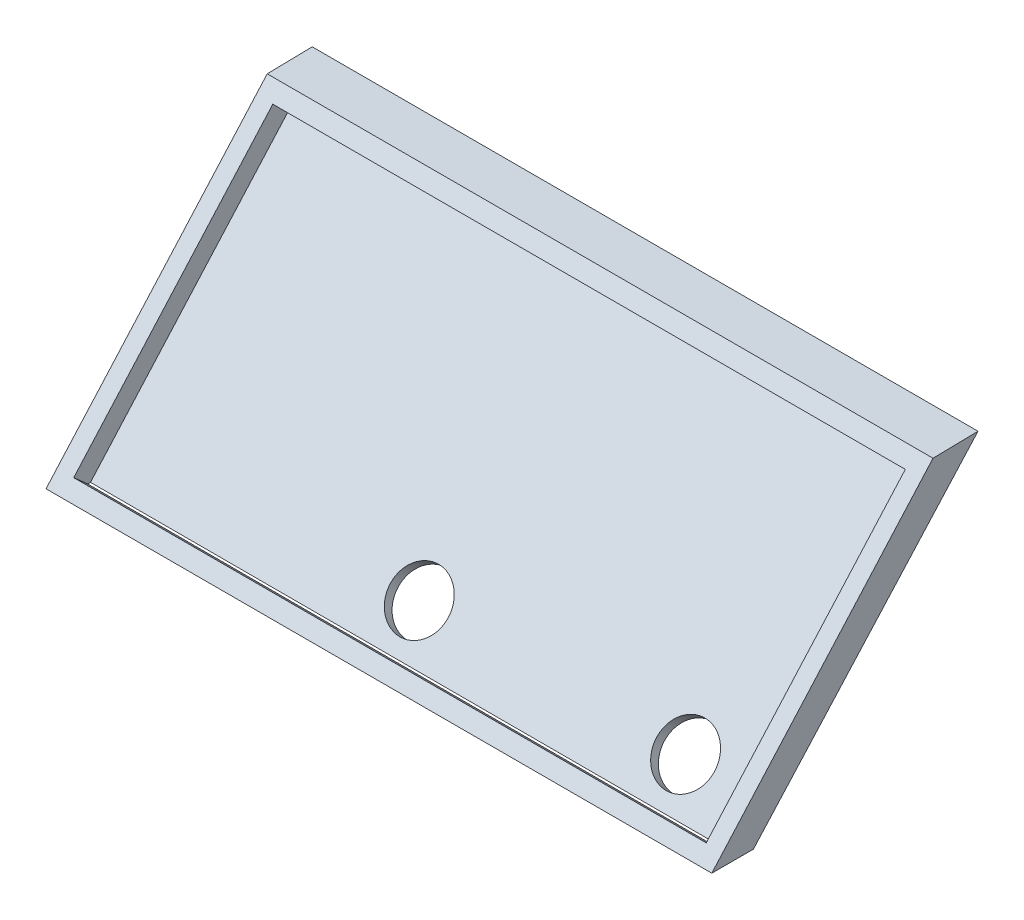
SolidWorks part; units mm, degrees
ref_plane "Front Plane" through (0, 0, 0) normal (0, 0, 1) x (1, 0, 0)
ref_plane "Top Plane" through (0, 0, 0) normal (0, 1, 0) x (1, 0, 0)
ref_plane "Right Plane" through (0, 0, 0) normal (1, 0, 0) x (0, 0, -1)
sketch "Sketch1" plane through (0, 0, 0) normal (0, 0, 1) x (1, 0, 0)
  line L1 (50.8, -25.4) -> (-50.8, -25.4)
  line L2 (50.8, -25.4) -> (50.8, 25.4)
  line L3 (50.8, 25.4) -> (-50.8, 25.4)
  line L4 (-50.8, -25.4) -> (-50.8, 25.4)
  line L5 (50.8, -25.4) -> (-50.8, 25.4) construction
  line L6 (50.8, 25.4) -> (-50.8, -25.4) construction
  point P0 (0, 0)
  dimension "D1" = 101.6
  dimension "D2" = 50.8
extrude "Boss-Extrude1" add sketch "Sketch1" against normal blind 228.6
sketch "Sketch2" plane through (0, 25.4, 0) normal (0, 1, 0) x (1, 0, 0)
  line L0 (0, 0) -> (0, 228.6) construction
  line L1 (50.8, 228.6) -> (-50.8, 228.6) construction
  line L3 (48.26, 200.66) -> (-48.26, 200.66)
  line L4 (48.26, 200.66) -> (48.26, 27.94)
  line L5 (48.26, 27.94) -> (-48.26, 27.94)
  line L6 (-48.26, 200.66) -> (-48.26, 27.94)
  line L7 (48.26, 200.66) -> (-48.26, 27.94) construction
  line L8 (48.26, 27.94) -> (-48.26, 200.66) construction
  point P6 (0, 114.3)
  dimension "D1" = 172.72
  dimension "D2" = 96.52
extrude "Cut-Extrude1" cut sketch "Sketch2" against normal blind 50.8
sketch "Sketch3" plane through (0, 25.4, 0) normal (0, 1, 0) x (1, 0, 0)
  line L0 (0, 0) -> (0, 76.1763)
  line L1 (-48.26, 200.66) -> (-48.26, 27.94) construction
  line L2 (48.26, 79.3513) -> (-48.26, 79.3513)
  line L3 (48.26, 79.3513) -> (48.26, 73.0013)
  line L4 (48.26, 73.0013) -> (-48.26, 73.0013)
  line L5 (-48.26, 79.3513) -> (-48.26, 73.0013)
  line L6 (48.26, 79.3513) -> (-48.26, 73.0013) construction
  line L7 (48.26, 73.0013) -> (-48.26, 79.3513) construction
  line M2 (-48.26, 27.94) -> (-48.26, 200.66)
  line M4 (48.26, 200.66) -> (48.26, 27.94)
  dimension "D1" = 6.35
extrude "Boss-Extrude2" add sketch "Sketch3" against normal blind 50.8 contours L4 L2 M4 M2 region at (47.2927, 25.4, -76.1763)
sketch "Sketch5" plane through (0, 25.4, 0) normal (0, 1, 0) x (1, 0, 0)
  line L0 (48.26, 73.0013) -> (50.8, 73.0013) construction
  line L3 (50.8, 228.6) -> (50.8, 0) construction
sketch "Sketch6" plane through (50.8, 0, 0) normal (1, 0, 0) x (0, 0, -1)
  line L0 (73.0013, 25.4) -> (106.7566, 63.3634)
  dimension "D1" = 50.8
sketch "Sketch7" plane through (0, 25.4, 0) normal (0, 1, 0) x (1, 0, 0)
  line L0 (48.26, 79.3513) -> (50.8, 79.3513)
  line L1 (50.8, 73.0013) -> (50.8, 106.7566) construction
sketch "Sketch8" plane through (50.8, 0, 0) normal (1, 0, 0) x (0, 0, -1)
  line L0 (79.3513, 25.4) -> (113.6226, 63.5)
  line L2 (106.7566, 63.3634) -> (113.6226, 63.5)
  dimension "D1" = 38.1
sketch "Sketch9" plane through (50.8, 0, 0) normal (1, 0, 0) x (0, 0, -1)
  line L0 (73.0013, 25.4) -> (79.3513, 25.4)
sketch "Sketch10" plane through (0, 25.4, 0) normal (0, 1, 0) x (1, 0, 0)
  line L0 (-48.26, 79.3513) -> (-50.8, 79.3513)
  line L1 (-50.8, 228.6) -> (-50.8, 0) construction
  line L2 (-48.26, 73.0013) -> (-50.8, 73.0013)
sketch "Sketch11" plane through (-50.8, 0, 0) normal (-1, 0, 0) x (0, 0, 1)
  line L0 (-79.3513, 25.4) -> (-113.6226, 63.5)
  line L1 (-73.0013, 25.4) -> (-106.7566, 63.3634)
  line L2 (-106.7566, 63.3634) -> (-113.6226, 63.5)
  line L3 (-79.3513, 25.4) -> (-73.0013, 25.4)
extrude "Boss-Extrude3" add sketch "Sketch11" against normal up to vertex (101.6 mm away) contours L1 L2 L0 L3 up to point (50.8, 63.3634, -106.7566)
sketch "Sketch13" plane through (0, 25.4, 0) normal (0, 1, 0) x (1, 0, 0)
  line L1 (-48.26, 200.66) -> (48.26, 200.66)
  line L2 (-48.26, 200.66) -> (-48.26, 226.06)
  line L3 (-48.26, 226.06) -> (48.26, 226.06)
  line L4 (48.26, 200.66) -> (48.26, 226.06)
  dimension "D1" = 25.4
extrude "Cut-Extrude2" cut sketch "Sketch13" against normal blind 50.8
sketch "Sketch14" plane through (0, 25.4, 0) normal (0, 1, 0) x (1, 0, 0)
  line L1 (-48.26, 27.94) -> (48.26, 27.94)
  line L2 (-48.26, 27.94) -> (-48.26, 2.54)
  line L3 (-48.26, 2.54) -> (48.26, 2.54)
  line L4 (48.26, 27.94) -> (48.26, 2.54)
  dimension "D1" = 96.52
  dimension "D2" = 25.4
extrude "Cut-Extrude3" cut sketch "Sketch14" against normal blind 50.8
sketch "Sketch15" plane through (0, 0, -73.0013) normal (0, 0, 1) x (1, 0, 0)
  line L1 (48.26, -25.4) -> (-48.26, -25.4)
  line L2 (48.26, -25.4) -> (48.26, 25.4)
  line L3 (48.26, 25.4) -> (-48.26, 25.4)
  line L4 (-48.26, -25.4) -> (-48.26, 25.4)
  line L5 (48.26, -25.4) -> (-48.26, 25.4) construction
  line L6 (48.26, 25.4) -> (-48.26, -25.4) construction
  point P0 (0, 0)
  dimension "D1" = 96.52
  dimension "D2" = 50.8
extrude "Cut-Extrude6" cut sketch "Sketch15" against normal blind 6.35
sketch "Sketch16" plane through (0, -25.0354, -28.1564) normal (0, 0.6645, 0.7473) x (1, 0, 0)
  line L0 (0, 67.4892) -> (0, 118.2892) construction
  line L1 (48.26, 67.4892) -> (-48.26, 67.4892) construction
  line L2 (50.8, 118.2892) -> (-50.8, 118.2892) construction
  line L4 (48.26, 70.0292) -> (-48.26, 70.0292)
  line L5 (48.26, 70.0292) -> (48.26, 115.7492)
  line L6 (48.26, 115.7492) -> (-48.26, 115.7492)
  line L7 (-48.26, 70.0292) -> (-48.26, 115.7492)
  line L8 (48.26, 70.0292) -> (-48.26, 115.7492) construction
  line L9 (48.26, 115.7492) -> (-48.26, 70.0292) construction
  point P7 (0, 92.8892)
  dimension "D1" = 96.52
  dimension "D2" = 45.72
extrude "Cut-Extrude7" cut sketch "Sketch16" against normal blind 3.175
sketch "Sketch17" plane through (0, 0, 0) normal (0, 0, 1) x (1, 0, 0)
  line L0 (50.8, 0) -> (-50.8, 0)
  line L1 (-50.8, 25.4) -> (-50.8, -25.4) construction
  line L4 (-50.8, 0) -> (-50.8, -25.4)
  line L5 (-50.8, -25.4) -> (50.8, -25.4)
  line L6 (50.8, 0) -> (50.8, -25.4)
  point P6 (0, 0)
extrude "Cut-Extrude8" cut sketch "Sketch17" against normal blind 228.6
sketch "Sketch18" plane through (48.26, 0, 0) normal (-1, 0, 0) x (0, 0, 1)
  line L0 (-73.0013, 25.4) -> (-73.0013, 0) construction
  line L1 (-228.6, 0) -> (0, 0) construction
  line L2 (-79.3513, 25.4) -> (-79.3513, 0) construction
  line L3 (-79.3513, 0) -> (-73.0013, 0) construction
  line L4 (-73.0013, 12.7) -> (-79.3513, 12.7) construction
sketch "Sketch19" plane through (48.26, 0, 0) normal (-1, 0, 0) x (0, 0, 1)
  line L0 (-73.0013, 12.7) -> (-79.3513, 12.7)
  line L1 (-79.3513, 12.7) -> (-79.3513, 0)
  line L2 (-79.3513, 0) -> (-73.0013, 0)
  line L3 (-73.0013, 12.7) -> (-73.0013, 0)
extrude "Boss-Extrude4" add sketch "Sketch19" along normal blind 96.52
sketch "Sketch20" plane through (-50.8, 0, 0) normal (-1, 0, 0) x (0, 0, 1)
  line L0 (-228.6, 0) -> (-177.8, 0)
  line L1 (-228.6, 0) -> (0, 0) construction
  line L3 (-177.8, 0) -> (-171.45, 0)
  line L4 (-177.8, 0) -> (-177.8, 12.7)
  line L5 (-177.8, 12.7) -> (-171.45, 12.7)
  line L6 (-171.45, 0) -> (-171.45, 12.7)
  line M4 (-228.6, 0) -> (0, 0)
  dimension "D1" = 50.8
  dimension "D2" = 6.35
  dimension "D3" = 12.7
extrude "Boss-Extrude5" add sketch "Sketch20" against normal blind 101.6 contours L6 L5 L4 M4 region at (-50.8, 6.35, -174.625)
sketch "Sketch24" plane through (0, 0, 0) normal (0, -1, 0) x (1, 0, 0)
  line L0 (48.26, -79.3513) -> (-48.26, -79.3513) construction
  line L1 (50.8, -73.0013) -> (38.1, -73.0013)
  line L2 (50.8, -73.0013) -> (50.8, -79.3513)
  line L3 (50.8, -79.3513) -> (38.1, -79.3513)
  line L4 (38.1, -73.0013) -> (38.1, -79.3513)
  dimension "D1" = 12.7
extrude "Boss-Extrude8" add sketch "Sketch24" along normal blind 19.05
sketch "Sketch25" plane through (0, 0, 0) normal (0, -1, 0) x (1, 0, 0)
  line L0 (-48.26, -79.3513) -> (38.1, -79.3513) construction
  line L1 (-50.8, -73.0013) -> (-38.1, -73.0013)
  line L2 (-50.8, -73.0013) -> (-50.8, -79.3513)
  line L3 (-50.8, -79.3513) -> (-38.1, -79.3513)
  line L4 (-38.1, -73.0013) -> (-38.1, -79.3513)
  dimension "D1" = 12.7
extrude "Boss-Extrude9" add sketch "Sketch25" along normal blind 19.05
sketch "Sketch26" plane through (0, 0, 0) normal (0, -1, 0) x (1, 0, 0)
  line L0 (-50.8, -228.6) -> (-50.8, -79.3513) construction
  line L1 (-50.8, -171.45) -> (-38.1, -171.45)
  line L2 (-50.8, -171.45) -> (-50.8, -177.8)
  line L3 (-50.8, -177.8) -> (-38.1, -177.8)
  line L4 (-38.1, -171.45) -> (-38.1, -177.8)
  line L5 (48.26, -177.8) -> (-48.26, -177.8) construction
  dimension "D1" = 12.7
extrude "Boss-Extrude10" add sketch "Sketch26" along normal blind 19.05
sketch "Sketch27" plane through (0, 0, 0) normal (0, -1, 0) x (1, 0, 0)
  line L0 (50.8, -228.6) -> (50.8, -79.3513) construction
  line L1 (50.8, -177.8) -> (38.1, -177.8)
  line L2 (50.8, -177.8) -> (50.8, -171.45)
  line L3 (50.8, -171.45) -> (38.1, -171.45)
  line L4 (38.1, -177.8) -> (38.1, -171.45)
  line L5 (48.26, -171.45) -> (-38.1, -171.45) construction
  dimension "D1" = 12.7
extrude "Boss-Extrude11" add sketch "Sketch27" along normal blind 19.05
sketch "Sketch28" plane through (0, 0, -73.0013) normal (0, 0, 1) x (1, 0, 0)
  line L0 (50.8, 0) -> (-50.8, 0) construction
  line L1 (50.8, -19.05) -> (41.91, -19.05)
  line L2 (50.8, -19.05) -> (50.8, 0)
  line L3 (50.8, 0) -> (41.91, 0)
  line L4 (41.91, -19.05) -> (41.91, 0)
  dimension "D1" = 8.89
extrude "Cut-Extrude9" cut sketch "Sketch28" against normal blind 6.35
sketch "Sketch29" plane through (0, 0, -73.0013) normal (0, 0, 1) x (1, 0, 0)
  line L0 (50.8, 0) -> (-50.8, 0) construction
  line L1 (-50.8, -19.05) -> (-41.91, -19.05)
  line L2 (-50.8, -19.05) -> (-50.8, 0)
  line L3 (-50.8, 0) -> (-41.91, 0)
  line L4 (-41.91, -19.05) -> (-41.91, 0)
  dimension "D1" = 8.89
extrude "Cut-Extrude10" cut sketch "Sketch29" against normal blind 6.35
sketch "Sketch30" plane through (0, 0, -171.45) normal (0, 0, 1) x (1, 0, 0)
  line L1 (-50.8, -19.05) -> (-41.91, -19.05)
  line L2 (-50.8, -19.05) -> (-50.8, 0)
  line L3 (-50.8, 0) -> (-41.91, 0)
  line L4 (-41.91, -19.05) -> (-41.91, 0)
extrude "Cut-Extrude11" cut sketch "Sketch30" against normal blind 6.35
sketch "Sketch31" plane through (0, 0, -171.45) normal (0, 0, 1) x (1, 0, 0)
  line L0 (41.91, 0) -> (41.91, -19.05) construction
  line L1 (50.8, -19.05) -> (41.91, -19.05)
  line L2 (50.8, -19.05) -> (50.8, 0)
  line L3 (50.8, 0) -> (41.91, 0)
  line L4 (41.91, -19.05) -> (41.91, 0)
extrude "Cut-Extrude12" cut sketch "Sketch31" against normal blind 6.35
sketch "Sketch33" plane through (0, 0, -2.54) normal (0, 0, -1) x (-1, 0, 0)
  line L1 (48.26, 0) -> (48.26, 25.4) construction
  line L2 (48.26, 12.7) -> (-48.26, 12.7) construction
  line L3 (-48.26, 0) -> (-48.26, 25.4) construction
  line L5 (48.26, 13.97) -> (-48.26, 13.97)
  line L6 (48.26, 13.97) -> (48.26, 11.43)
  line L7 (48.26, 11.43) -> (-48.26, 11.43)
  line L8 (-48.26, 13.97) -> (-48.26, 11.43)
  line L9 (48.26, 13.97) -> (-48.26, 11.43) construction
  line L10 (48.26, 11.43) -> (-48.26, 13.97) construction
  point P6 (0, 12.7)
  dimension "D1" = 2.54
extrude "Boss-Extrude13" add sketch "Sketch33" along normal blind 2.54
sketch "Sketch34" plane through (0, 0, -226.06) normal (0, 0, 1) x (1, 0, 0)
  line L0 (0, 0) -> (0, 25.4) construction
  line L1 (-48.26, 0) -> (-48.26, 25.4) construction
  line L2 (48.26, 12.7) -> (-48.26, 12.7) construction
  line L3 (48.26, 0) -> (48.26, 25.4) construction
  line L4 (-48.26, 0) -> (48.26, 0) construction
  line L5 (48.26, 25.4) -> (-48.26, 25.4) construction
  line L7 (48.26, 13.97) -> (-48.26, 13.97)
  line L8 (48.26, 13.97) -> (48.26, 11.43)
  line L9 (48.26, 11.43) -> (-48.26, 11.43)
  line L10 (-48.26, 13.97) -> (-48.26, 11.43)
  line L11 (48.26, 13.97) -> (-48.26, 11.43) construction
  line L12 (48.26, 11.43) -> (-48.26, 13.97) construction
  point P12 (0, 12.7)
  dimension "D1" = 2.54
extrude "Boss-Extrude17" add sketch "Sketch34" along normal blind 2.54
sketch "Sketch36" plane through (-48.26, 0, 0) normal (1, 0, 0) x (0, 0, -1)
  line L0 (5.08, 11.43) -> (5.08, 13.97) construction
  line L1 (5.08, 13.97) -> (223.52, 13.97)
  line L2 (5.08, 13.97) -> (5.08, 11.43)
  line L3 (5.08, 11.43) -> (223.52, 11.43)
  line L4 (223.52, 13.97) -> (223.52, 11.43)
extrude "Boss-Extrude18" add sketch "Sketch36" along normal blind 2.54
sketch "Sketch37" plane through (48.26, 0, 0) normal (-1, 0, 0) x (0, 0, 1)
  line L1 (-5.08, 13.97) -> (-223.52, 13.97)
  line L2 (-5.08, 13.97) -> (-5.08, 11.43)
  line L3 (-5.08, 11.43) -> (-223.52, 11.43)
  line L4 (-223.52, 13.97) -> (-223.52, 11.43)
extrude "Boss-Extrude19" add sketch "Sketch37" along normal blind 2.54
sketch "Sketch42" plane through (-41.91, 0, 0) normal (-1, 0, 0) x (0, 0, 1)
  line L0 (-73.0013, -19.05) -> (-73.0013, 0) construction
  line L1 (-73.0013, -12.7) -> (-79.3513, -12.7)
  line L2 (-73.0013, -12.7) -> (-73.0013, -19.05)
  line L3 (-73.0013, -19.05) -> (-79.3513, -19.05)
  line L4 (-79.3513, -12.7) -> (-79.3513, -19.05)
  line L5 (-79.3513, -19.05) -> (-79.3513, 0) construction
extrude "Cut-Extrude16" cut sketch "Sketch42" against normal blind 5.08
sketch "Sketch45" plane through (0, 0, 0) normal (0, 0, 1) x (1, 0, 0)
  line L0 (-50.8, 12.7) -> (50.8, 12.7) construction
  line L1 (-50.8, 25.4) -> (-50.8, 0) construction
  line L2 (50.8, 0) -> (50.8, 25.4) construction
  line L3 (0, 0) -> (0, 25.4) construction
  line L4 (48.26, 25.4) -> (-48.26, 25.4) construction
  line L5 (0, 12.7) -> (-50.8, 12.7) construction
  line L6 (-25.0661, 12.7) -> (-50.8, 12.7) construction
  line L7 (44.537, 17.78) -> (44.537, 7.62)
  line L8 (-31.329, 17.78) -> (-44.537, 17.78)
  line L9 (-31.329, 17.78) -> (-31.329, 7.62)
  line L10 (-31.329, 7.62) -> (-44.537, 7.62)
  line L11 (-44.537, 17.78) -> (-44.537, 7.62)
  line L12 (-31.329, 17.78) -> (-44.537, 7.62) construction
  line L13 (-31.329, 7.62) -> (-44.537, 17.78) construction
  line L14 (31.329, 7.62) -> (44.537, 7.62)
  line L15 (31.329, 17.78) -> (31.329, 7.62)
  line L16 (31.329, 17.78) -> (44.537, 17.78)
  point P13 (-37.933, 12.7)
  dimension "D1" = 13.208
  dimension "D2" = 10.16
extrude "Cut-Extrude19" cut sketch "Sketch45" against normal blind 6.35
sketch "Sketch50" plane through (-41.91, 0, 0) normal (-1, 0, 0) x (0, 0, 1)
  line L0 (-79.3513, -12.7) -> (-79.3513, -19.05)
  line L1 (-73.0013, -12.7) -> (-73.0013, -19.05)
  line L2 (-79.3513, -19.05) -> (-73.0013, -19.05)
  line L7 (-79.3513, 0) -> (-79.3513, -12.7)
  line L8 (-79.3513, -12.7) -> (-73.0013, -12.7)
  line L9 (-73.0013, -12.7) -> (-73.0013, 0)
  line L10 (-73.0013, 0) -> (-79.3513, 0)
  line L12 (-79.3513, -12.7) -> (-73.0013, -12.7)
  dimension "D1" = 6.35
  dimension "D2" = 0
extrude "Boss-Extrude20" add sketch "Sketch50" against normal blind 3.81 contours L0 L2 L1 L12
sketch "Sketch51" plane through (-41.91, 0, 0) normal (-1, 0, 0) x (0, 0, 1)
  line L0 (-79.3513, -19.05) -> (-79.3513, -25.4)
  line L1 (-73.0013, -19.05) -> (-73.0013, -25.4)
  line L2 (-73.0013, -25.4) -> (-79.3513, -25.4)
  line L7 (-79.3513, 0) -> (-79.3513, -19.05)
  line L8 (-79.3513, -19.05) -> (-73.0013, -19.05)
  line L9 (-73.0013, -19.05) -> (-73.0013, 0)
  line L10 (-73.0013, 0) -> (-79.3513, 0)
  line L12 (-79.3513, -19.05) -> (-73.0013, -19.05)
  dimension "D1" = 6.35
  dimension "D2" = 0
extrude "Boss-Extrude21" add sketch "Sketch51" against normal blind 3.81
sketch "Sketch52" plane through (-41.91, 0, 0) normal (-1, 0, 0) x (0, 0, 1)
  line L0 (-177.8, -19.05) -> (-177.8, -25.4)
  line L1 (-171.45, -19.05) -> (-171.45, -25.4)
  line L2 (-171.45, -25.4) -> (-177.8, -25.4)
  line L7 (-171.45, -19.05) -> (-171.45, 0)
  line L8 (-171.45, 0) -> (-177.8, 0)
  line L9 (-177.8, 0) -> (-177.8, -19.05)
  line L10 (-177.8, -19.05) -> (-171.45, -19.05)
  line L14 (-177.8, -19.05) -> (-171.45, -19.05)
  dimension "D1" = 6.35
  dimension "D2" = 0
extrude "Boss-Extrude22" add sketch "Sketch52" against normal blind 3.81
sketch "Sketch53" plane through (41.91, 0, 0) normal (1, 0, 0) x (0, 0, -1)
  line L0 (73.0013, -19.05) -> (73.0013, -25.4)
  line L1 (79.3513, -25.4) -> (79.3513, -19.05)
  line L2 (79.3513, -25.4) -> (79.3513, 0) construction
  line L3 (79.3513, 0) -> (79.3513, -19.05) construction
  line L4 (73.0013, -25.4) -> (79.3513, -25.4)
  line L5 (73.0013, -19.05) -> (79.3513, -19.05)
extrude "Boss-Extrude23" add sketch "Sketch53" against normal blind 3.81
sketch "Sketch54" plane through (41.91, 0, 0) normal (1, 0, 0) x (0, 0, -1)
  line L0 (171.45, -19.05) -> (171.45, -25.4)
  line L1 (177.8, -25.4) -> (171.45, -25.4) construction
  line L2 (171.45, -25.4) -> (171.45, 0) construction
  line L3 (171.45, -25.4) -> (177.8, -25.4)
  line L4 (177.8, -25.4) -> (177.8, -19.05)
  line L5 (177.8, -19.05) -> (171.45, -19.05)
extrude "Boss-Extrude24" add sketch "Sketch54" against normal blind 3.81
sketch "Sketch55" plane through (0, -25.4, 0) normal (0, -1, 0) x (1, 0, 0)
  line L0 (0, -226.06) -> (0, -2.54) construction
  line L1 (-48.26, -226.06) -> (48.26, -226.06) construction
  line L2 (48.26, -2.54) -> (-48.26, -2.54) construction
  line L4 (38.1, -25.4) -> (-38.1, -25.4)
  line L5 (38.1, -25.4) -> (38.1, -203.2)
  line L6 (38.1, -203.2) -> (-38.1, -203.2)
  line L7 (-38.1, -25.4) -> (-38.1, -203.2)
  line L8 (38.1, -25.4) -> (-38.1, -203.2) construction
  line L9 (38.1, -203.2) -> (-38.1, -25.4) construction
  point P6 (0, -114.3)
  dimension "D1" = 177.8
  dimension "D2" = 76.2
extrude "Boss-Extrude25" add sketch "Sketch55" against normal blind 7.62
sketch "Sketch56" plane through (-41.91, 0, 0) normal (-1, 0, 0) x (0, 0, 1)
  line L0 (-79.3513, -21.59) -> (-73.0013, -21.59) construction
  line L1 (-79.3513, -25.4) -> (-79.3513, -17.78) construction
  line L2 (-73.0013, -25.4) -> (-73.0013, -17.78) construction
  circle A0 centre (-76.1763, -21.59) radius 2.54
  dimension "D1" = 5.08
extrude "Cut-Extrude20" cut sketch "Sketch56" against normal blind 83.82
sketch "Sketch57" plane through (-41.91, 0, 0) normal (-1, 0, 0) x (0, 0, 1)
  line L0 (-177.8, -21.59) -> (-171.45, -21.59) construction
  line L1 (-177.8, -25.4) -> (-177.8, -17.78) construction
  line L2 (-171.45, -25.4) -> (-171.45, 0) construction
  circle A0 centre (-174.625, -21.59) radius 2.54
  dimension "D1" = 5.08
extrude "Cut-Extrude21" cut sketch "Sketch57" against normal blind 83.82
sketch "Sketch59" plane through (-50.8, 0, 0) normal (-1, 0, 0) x (0, 0, 1)
  line L0 (-79.3513, 25.4) -> (-73.0013, 25.4)
extrude "Cut-Extrude22" cut sketch "Sketch59" against normal blind 101.6 and the other way through all flip side to cut
sketch "Sketch60" plane through (0, -27.1451, -30.5291) normal (0, 0.6645, 0.7473) x (1, 0, 0)
  line L0 (44.85, 67.4892) -> (44.85, 77.0142) construction
  line L1 (50.8, 67.4892) -> (-50.8, 67.4892) construction
  line L2 (50.8, 77.0142) -> (38.1, 77.0142) construction
  line L3 (50.8, 67.4892) -> (50.8, 118.2892) construction
  circle A0 centre (38.1, 77.0142) radius 4.445
  dimension "D3" = 8.89
  dimension "D1" = 9.525
  dimension "D2" = 12.7
extrude "Cut-Extrude23" cut sketch "Sketch60" against normal blind 2.54
sketch "Sketch61" plane through (0, -27.1451, -30.5291) normal (0, 0.6645, 0.7473) x (1, 0, 0)
  line L0 (-23.2413, 67.4892) -> (-23.2413, 77.0142) construction
  line L1 (50.8, 67.4892) -> (-50.8, 67.4892) construction
  line L2 (-50.8, 77.0142) -> (-2.54, 77.0142) construction
  line L3 (-50.8, 67.4892) -> (-50.8, 118.2892) construction
  circle A0 centre (-2.54, 77.0142) radius 4.445
  dimension "D3" = 8.89
  dimension "D1" = 9.525
  dimension "D2" = 48.26
extrude "Cut-Extrude24" cut sketch "Sketch61" against normal blind 2.54
